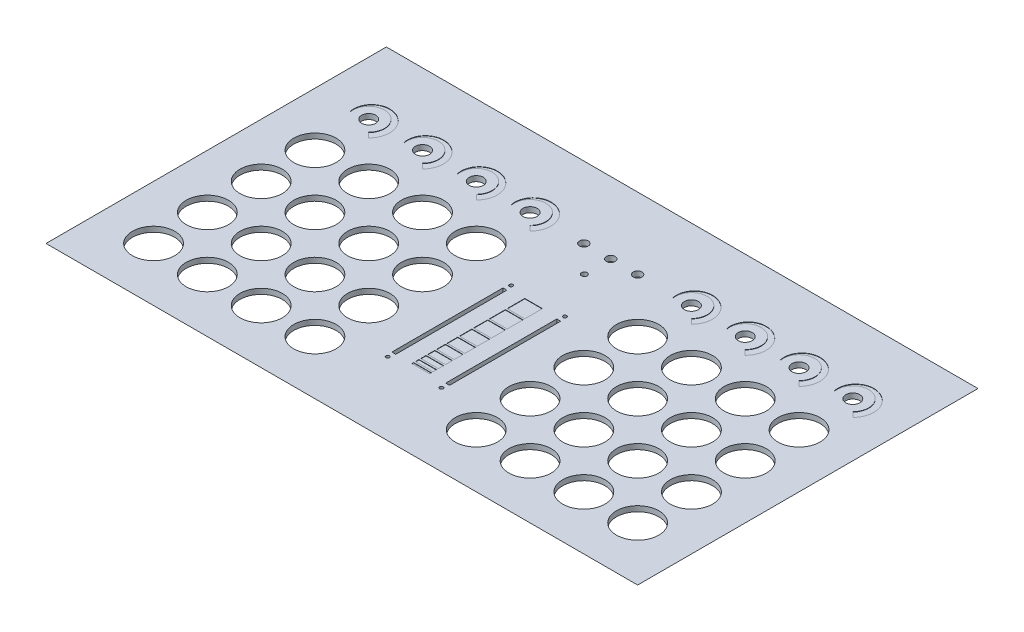
SolidWorks part; units mm, degrees
material "ABS"
ref_plane "Front Plane" through (0, 0, 0) normal (0, 0, 1) x (1, 0, 0)
ref_plane "Top Plane" through (0, 0, 0) normal (0, 1, 0) x (1, 0, 0)
ref_plane "Right Plane" through (0, 0, 0) normal (1, 0, 0) x (0, 0, -1)
sketch "Sketch2" plane through (0, 0, 0) normal (0, 1, 0) x (1, 0, 0)
  line L0 (0, 0) -> (91.5, 0) construction
  line L1 (0, 0) -> (0, 91.5) construction
  line L2 (122, 80.75) -> (122, 10.75) construction
  line L3 (120.9, 77.25) -> (123.1, 77.25)
  line L4 (120.9, 77.25) -> (120.9, 14.25)
  line L5 (120.9, 14.25) -> (123.1, 14.25)
  line L6 (123.1, 77.25) -> (123.1, 14.25)
  line L7 (91.5, 45.75) -> (137.25, 45.75) construction
  line L8 (91.5, 30.5) -> (91.5, 61) construction
  line L9 (0, 91.5) -> (0, 122) construction
  line L10 (0, 122) -> (91.5, 122) construction
  line L11 (0, 122) -> (30.5, 122) construction
  line L12 (137.25, -28.4189) -> (137.25, 162.5507) construction
  line L13 (274.5, 122) -> (244, 122) construction
  line L14 (274.5, 122) -> (183, 122) construction
  line L15 (274.5, 91.5) -> (274.5, 122) construction
  line L16 (183, 30.5) -> (183, 61) construction
  line L17 (152.5, 80.75) -> (152.5, 10.75) construction
  line L18 (274.5, 0) -> (274.5, 91.5) construction
  line L19 (274.5, 0) -> (183, 0) construction
  line L20 (151.4, 77.25) -> (151.4, 14.25)
  line L21 (153.6, 14.25) -> (151.4, 14.25)
  line L22 (153.6, 77.25) -> (153.6, 14.25)
  line L23 (153.6, 77.25) -> (151.4, 77.25)
  line L25 (-30.5, -30.5) -> (305, -30.5)
  line L26 (-30.5, -30.5) -> (-30.5, 162.5)
  line L27 (-30.5, 162.5) -> (305, 162.5)
  line L28 (305, -30.5) -> (305, 162.5)
  circle A0 centre (0, 0) radius 12
  circle A1 centre (30.5, 0) radius 12
  circle A2 centre (61, 0) radius 12
  circle A3 centre (91.5, 0) radius 12
  circle A4 centre (30.5, 30.5) radius 12
  circle A5 centre (61, 30.5) radius 12
  circle A6 centre (91.5, 30.5) radius 12
  circle A7 centre (30.5, 61) radius 12
  circle A8 centre (61, 61) radius 12
  circle A9 centre (91.5, 61) radius 12
  circle A10 centre (30.5, 91.5) radius 12
  circle A11 centre (61, 91.5) radius 12
  circle A12 centre (91.5, 91.5) radius 12
  circle A13 centre (0, 30.5) radius 12
  circle A14 centre (0, 61) radius 12
  circle A15 centre (0, 91.5) radius 12
  circle A16 centre (122, 80.75) radius 1
  circle A17 centre (122, 10.75) radius 1
  circle A18 centre (0, 122) radius 4
  circle A19 centre (30.5, 122) radius 4
  circle A20 centre (61, 122) radius 4
  circle A21 centre (91.5, 122) radius 4
  circle A22 centre (183, 122) radius 4
  circle A23 centre (213.5, 122) radius 4
  circle A24 centre (244, 122) radius 4
  circle A25 centre (274.5, 122) radius 4
  circle A26 centre (152.5, 10.75) radius 1
  circle A27 centre (152.5, 80.75) radius 1
  circle A28 centre (274.5, 91.5) radius 12
  circle A29 centre (274.5, 61) radius 12
  circle A30 centre (274.5, 30.5) radius 12
  circle A31 centre (183, 91.5) radius 12
  circle A32 centre (213.5, 91.5) radius 12
  circle A33 centre (244, 91.5) radius 12
  circle A34 centre (183, 61) radius 12
  circle A35 centre (213.5, 61) radius 12
  circle A36 centre (244, 61) radius 12
  circle A37 centre (183, 30.5) radius 12
  circle A38 centre (213.5, 30.5) radius 12
  circle A39 centre (244, 30.5) radius 12
  circle A40 centre (183, 0) radius 12
  circle A41 centre (213.5, 0) radius 12
  circle A42 centre (244, 0) radius 12
  circle A43 centre (274.5, 0) radius 12
  point P41 (122, 77.25)
  point P42 (120.9, 45.75)
  point P105 (153.6, 45.75)
  point P106 (152.5, 77.25)
  dimension "D1" = 24
  dimension "D8" = 2
  dimension "D12" = 8
  dimension "D4" = 30.5
  dimension "D5" = 30.5
  dimension "D6" = 63
  dimension "D7" = 2.2
  dimension "D9" = 3.5
  dimension "D10" = 3.5
  dimension "D11" = 30.5
  dimension "D14" = 30.5
  dimension "D15" = 30.5
  dimension "D16" = 15.25
  dimension "D17" = 30.5
  dimension "D18" = 30.5
  dimension "D19" = 30.5
  dimension "D20" = 40.5
  dimension "D2" = 4
  dimension "D3" = 4
  dimension "D13" = 4
extrude "Boss-Extrude1" add sketch "Sketch2" along normal blind 3
sketch "Sketch27" plane through (0, 3, 0) normal (0, 1, 0) x (1, 0, 0)
  line L0 (0, 122) -> (-6.364, 115.636) construction
  line L1 (-6.364, 115.636) -> (6.364, 115.636) construction
  line L2 (6.364, 115.636) -> (0, 122) construction
  line L3 (0, 131) -> (0, 135) construction
  line L4 (6.364, 115.636) -> (9.1924, 112.8076)
  line L5 (0, 122) -> (0.8429, 122.8429) construction
  line L6 (36.864, 115.636) -> (39.6924, 112.8076)
  line L7 (30.5, 122) -> (24.136, 115.636) construction
  line L8 (24.136, 115.636) -> (36.864, 115.636) construction
  line L9 (36.864, 115.636) -> (30.5, 122) construction
  line L10 (30.5, 131) -> (30.5, 135) construction
  line L11 (30.5, 122) -> (31.3429, 122.8429) construction
  line L12 (67.364, 115.636) -> (70.1924, 112.8076)
  line L13 (61, 122) -> (54.636, 115.636) construction
  line L14 (54.636, 115.636) -> (67.364, 115.636) construction
  line L15 (67.364, 115.636) -> (61, 122) construction
  line L16 (61, 131) -> (61, 135) construction
  line L17 (61, 122) -> (61.8429, 122.8429) construction
  line L18 (97.864, 115.636) -> (100.6924, 112.8076)
  line L19 (91.5, 122) -> (85.136, 115.636) construction
  line L20 (85.136, 115.636) -> (97.864, 115.636) construction
  line L21 (97.864, 115.636) -> (91.5, 122) construction
  line L22 (91.5, 131) -> (91.5, 135) construction
  line L23 (91.5, 122) -> (92.3429, 122.8429) construction
  line L24 (189.364, 115.636) -> (192.1924, 112.8076)
  line L25 (219.864, 115.636) -> (222.6924, 112.8076)
  line L26 (250.364, 115.636) -> (253.1924, 112.8076)
  line L27 (280.864, 115.636) -> (283.6924, 112.8076)
  line L28 (183, 122) -> (176.636, 115.636) construction
  line L29 (176.636, 115.636) -> (189.364, 115.636) construction
  line L30 (189.364, 115.636) -> (183, 122) construction
  line L31 (183, 131) -> (183, 135) construction
  line L32 (183, 122) -> (183.8429, 122.8429) construction
  line L33 (213.5, 122) -> (207.136, 115.636) construction
  line L34 (207.136, 115.636) -> (219.864, 115.636) construction
  line L35 (219.864, 115.636) -> (213.5, 122) construction
  line L36 (213.5, 131) -> (213.5, 135) construction
  line L37 (213.5, 122) -> (214.3429, 122.8429) construction
  line L38 (244, 122) -> (237.636, 115.636) construction
  line L39 (237.636, 115.636) -> (250.364, 115.636) construction
  line L40 (250.364, 115.636) -> (244, 122) construction
  line L41 (244, 131) -> (244, 135) construction
  line L42 (244, 122) -> (244.8429, 122.8429) construction
  line L43 (274.5, 122) -> (268.136, 115.636) construction
  line L44 (268.136, 115.636) -> (280.864, 115.636) construction
  line L45 (280.864, 115.636) -> (274.5, 122) construction
  line L46 (274.5, 131) -> (274.5, 135) construction
  line L47 (274.5, 122) -> (275.3429, 122.8429) construction
  line L48 (123.1, 14.25) -> (151.4, 14.25) construction
  line L49 (123.1, 77.25) -> (151.4, 77.25) construction
  line L50 (137.25, 14.25) -> (137.25, 77.25) construction
  line L51 (132.25, 15.25) -> (142.25, 15.25)
  line L52 (132.25, 14.25) -> (142.25, 14.25)
  line L53 (132.25, 47.25) -> (132.25, 48.25)
  line L54 (132.25, 14.25) -> (132.25, 15.25)
  line L55 (132.25, 15.25) -> (142.25, 15.25)
  line L56 (142.25, 14.25) -> (142.25, 15.25)
  line L57 (132.25, 16.25) -> (142.25, 16.25)
  line L58 (142.25, 47.25) -> (142.25, 48.25)
  line L59 (132.25, 16.25) -> (142.25, 16.25)
  line L60 (132.25, 16.25) -> (132.25, 17.25)
  line L61 (132.25, 77.25) -> (132.25, 78.25)
  line L62 (142.25, 16.25) -> (142.25, 17.25)
  line L63 (132.25, 78.25) -> (142.25, 78.25)
  line L64 (132.25, 17.25) -> (132.25, 18.25)
  line L65 (132.25, 18.25) -> (142.25, 18.25)
  line L66 (142.25, 17.25) -> (142.25, 18.25)
  line L67 (132.25, 18.25) -> (142.25, 18.25)
  line L68 (142.25, 78.25) -> (142.25, 77.25)
  line L69 (132.25, 19.25) -> (142.25, 19.25)
  line L71 (132.25, 19.25) -> (142.25, 19.25)
  line L72 (132.25, 19.25) -> (132.25, 20.25)
  line L74 (142.25, 19.25) -> (142.25, 20.25)
  line L76 (132.25, 20.25) -> (132.25, 21.25)
  line L78 (142.25, 20.25) -> (142.25, 21.25)
  line L80 (132.25, 21.25) -> (132.25, 22.25)
  line L81 (132.25, 22.25) -> (142.25, 22.25)
  line L82 (142.25, 21.25) -> (142.25, 22.25)
  line L83 (132.25, 22.25) -> (142.25, 22.25)
  line L85 (132.25, 23.25) -> (142.25, 23.25)
  line L87 (132.25, 23.25) -> (142.25, 23.25)
  line L88 (132.25, 23.25) -> (132.25, 24.25)
  line L90 (142.25, 23.25) -> (142.25, 24.25)
  line L92 (132.25, 24.25) -> (132.25, 25.25)
  line L94 (142.25, 24.25) -> (142.25, 25.25)
  line L96 (132.25, 25.25) -> (132.25, 26.25)
  line L98 (142.25, 25.25) -> (142.25, 26.25)
  line L100 (132.25, 26.25) -> (132.25, 27.25)
  line L101 (132.25, 27.25) -> (142.25, 27.25)
  line L102 (142.25, 26.25) -> (142.25, 27.25)
  line L103 (132.25, 27.25) -> (142.25, 27.25)
  line L105 (132.25, 28.25) -> (142.25, 28.25)
  line L107 (132.25, 28.25) -> (142.25, 28.25)
  line L108 (132.25, 28.25) -> (132.25, 29.25)
  line L110 (142.25, 28.25) -> (142.25, 29.25)
  line L112 (132.25, 29.25) -> (132.25, 30.25)
  line L114 (142.25, 29.25) -> (142.25, 30.25)
  line L116 (132.25, 30.25) -> (132.25, 31.25)
  line L118 (142.25, 30.25) -> (142.25, 31.25)
  line L120 (132.25, 31.25) -> (132.25, 32.25)
  line L122 (142.25, 31.25) -> (142.25, 32.25)
  line L124 (132.25, 32.25) -> (132.25, 33.25)
  line L125 (132.25, 33.25) -> (142.25, 33.25)
  line L126 (142.25, 32.25) -> (142.25, 33.25)
  line L127 (132.25, 33.25) -> (142.25, 33.25)
  line L129 (132.25, 34.25) -> (142.25, 34.25)
  line L131 (132.25, 34.25) -> (142.25, 34.25)
  line L132 (132.25, 34.25) -> (132.25, 35.25)
  line L134 (142.25, 34.25) -> (142.25, 35.25)
  line L136 (132.25, 35.25) -> (132.25, 36.25)
  line L138 (142.25, 35.25) -> (142.25, 36.25)
  line L140 (132.25, 36.25) -> (132.25, 37.25)
  line L142 (142.25, 36.25) -> (142.25, 37.25)
  line L144 (132.25, 37.25) -> (132.25, 38.25)
  line L146 (142.25, 37.25) -> (142.25, 38.25)
  line L148 (132.25, 38.25) -> (132.25, 39.25)
  line L150 (142.25, 38.25) -> (142.25, 39.25)
  line L152 (132.25, 39.25) -> (132.25, 40.25)
  line L153 (132.25, 40.25) -> (142.25, 40.25)
  line L154 (142.25, 39.25) -> (142.25, 40.25)
  line L155 (132.25, 40.25) -> (142.25, 40.25)
  line L157 (132.25, 41.25) -> (142.25, 41.25)
  line L159 (132.25, 41.25) -> (142.25, 41.25)
  line L160 (132.25, 41.25) -> (132.25, 42.25)
  line L162 (142.25, 41.25) -> (142.25, 42.25)
  line L164 (132.25, 42.25) -> (132.25, 43.25)
  line L166 (142.25, 42.25) -> (142.25, 43.25)
  line L168 (132.25, 43.25) -> (132.25, 44.25)
  line L170 (142.25, 43.25) -> (142.25, 44.25)
  line L172 (132.25, 44.25) -> (132.25, 45.25)
  line L174 (142.25, 44.25) -> (142.25, 45.25)
  line L176 (132.25, 45.25) -> (132.25, 46.25)
  line L178 (142.25, 45.25) -> (142.25, 46.25)
  line L180 (132.25, 46.25) -> (132.25, 47.25)
  line L182 (142.25, 46.25) -> (142.25, 47.25)
  line L185 (132.25, 48.25) -> (142.25, 48.25)
  line L187 (132.25, 48.25) -> (142.25, 48.25)
  line L189 (132.25, 49.25) -> (142.25, 49.25)
  line L191 (132.25, 49.25) -> (142.25, 49.25)
  line L192 (132.25, 49.25) -> (132.25, 50.25)
  line L194 (142.25, 49.25) -> (142.25, 50.25)
  line L196 (132.25, 50.25) -> (132.25, 51.25)
  line L198 (142.25, 50.25) -> (142.25, 51.25)
  line L200 (132.25, 51.25) -> (132.25, 52.25)
  line L202 (142.25, 51.25) -> (142.25, 52.25)
  line L204 (132.25, 52.25) -> (132.25, 53.25)
  line L206 (142.25, 52.25) -> (142.25, 53.25)
  line L208 (132.25, 53.25) -> (132.25, 54.25)
  line L210 (142.25, 53.25) -> (142.25, 54.25)
  line L212 (132.25, 54.25) -> (132.25, 55.25)
  line L214 (142.25, 54.25) -> (142.25, 55.25)
  line L216 (132.25, 55.25) -> (132.25, 56.25)
  line L218 (142.25, 55.25) -> (142.25, 56.25)
  line L220 (132.25, 56.25) -> (132.25, 57.25)
  line L221 (132.25, 57.25) -> (142.25, 57.25)
  line L222 (142.25, 56.25) -> (142.25, 57.25)
  line L223 (132.25, 57.25) -> (142.25, 57.25)
  line L225 (132.25, 58.25) -> (142.25, 58.25)
  line L227 (132.25, 58.25) -> (142.25, 58.25)
  line L228 (132.25, 58.25) -> (132.25, 59.25)
  line L230 (142.25, 58.25) -> (142.25, 59.25)
  line L232 (132.25, 59.25) -> (132.25, 60.25)
  line L234 (142.25, 59.25) -> (142.25, 60.25)
  line L236 (132.25, 60.25) -> (132.25, 61.25)
  line L238 (142.25, 60.25) -> (142.25, 61.25)
  line L240 (132.25, 61.25) -> (132.25, 62.25)
  line L242 (142.25, 61.25) -> (142.25, 62.25)
  line L244 (132.25, 62.25) -> (132.25, 63.25)
  line L246 (142.25, 62.25) -> (142.25, 63.25)
  line L248 (132.25, 63.25) -> (132.25, 64.25)
  line L250 (142.25, 63.25) -> (142.25, 64.25)
  line L252 (132.25, 64.25) -> (132.25, 65.25)
  line L254 (142.25, 64.25) -> (142.25, 65.25)
  line L256 (132.25, 65.25) -> (132.25, 66.25)
  line L258 (142.25, 65.25) -> (142.25, 66.25)
  line L260 (132.25, 66.25) -> (132.25, 67.25)
  line L261 (132.25, 67.25) -> (142.25, 67.25)
  line L262 (142.25, 66.25) -> (142.25, 67.25)
  line L263 (132.25, 67.25) -> (142.25, 67.25)
  line L265 (132.25, 68.25) -> (142.25, 68.25)
  line L267 (132.25, 68.25) -> (142.25, 68.25)
  line L268 (132.25, 68.25) -> (132.25, 69.25)
  line L270 (142.25, 68.25) -> (142.25, 69.25)
  line L272 (132.25, 69.25) -> (132.25, 70.25)
  line L274 (142.25, 69.25) -> (142.25, 70.25)
  line L276 (132.25, 70.25) -> (132.25, 71.25)
  line L278 (142.25, 70.25) -> (142.25, 71.25)
  line L280 (132.25, 71.25) -> (132.25, 72.25)
  line L282 (142.25, 71.25) -> (142.25, 72.25)
  line L284 (132.25, 72.25) -> (132.25, 73.25)
  line L286 (142.25, 72.25) -> (142.25, 73.25)
  line L288 (132.25, 73.25) -> (132.25, 74.25)
  line L290 (142.25, 73.25) -> (142.25, 74.25)
  line L292 (132.25, 74.25) -> (132.25, 75.25)
  line L294 (142.25, 74.25) -> (142.25, 75.25)
  line L296 (132.25, 75.25) -> (132.25, 76.25)
  line L298 (142.25, 75.25) -> (142.25, 76.25)
  line L300 (132.25, 76.25) -> (132.25, 77.25)
  line L302 (142.25, 76.25) -> (142.25, 77.25)
  line L303 (142.25, 15.25) -> (142.25, 16.25) [skipped]
  line L304 (132.25, 15.25) -> (132.25, 16.25) [skipped]
  line L305 (137.25, 17.25) -> (142.25, 17.25) [skipped]
  line L306 (137.25, 17.25) -> (142.25, 17.25) [skipped]
  line L307 (132.25, 18.25) -> (132.25, 19.25) [skipped]
  line L308 (142.25, 18.25) -> (142.25, 19.25) [skipped]
  line L309 (132.25, 20.25) -> (137.25, 20.25) [skipped]
  line L310 (132.25, 20.25) -> (137.25, 20.25) [skipped]
  line L311 (132.25, 21.25) -> (137.25, 21.25) [skipped]
  line L312 (132.25, 21.25) -> (137.25, 21.25) [skipped]
  line L313 (132.25, 22.25) -> (132.25, 23.25) [skipped]
  line L314 (142.25, 22.25) -> (142.25, 23.25) [skipped]
  line L315 (132.25, 24.25) -> (137.25, 24.25) [skipped]
  line L316 (132.25, 24.25) -> (137.25, 24.25) [skipped]
  line L317 (132.25, 25.25) -> (137.25, 25.25) [skipped]
  line L318 (132.25, 25.25) -> (137.25, 25.25) [skipped]
  line L319 (132.25, 26.25) -> (137.25, 26.25) [skipped]
  line L320 (132.25, 26.25) -> (137.25, 26.25) [skipped]
  line L321 (132.25, 27.25) -> (132.25, 28.25) [skipped]
  line L322 (142.25, 27.25) -> (142.25, 28.25) [skipped]
  line L323 (132.25, 32.25) -> (137.25, 32.25) [skipped]
  line L324 (132.25, 32.25) -> (137.25, 32.25) [skipped]
  line L325 (132.25, 31.25) -> (137.25, 31.25) [skipped]
  line L326 (132.25, 31.25) -> (137.25, 31.25) [skipped]
  line L327 (132.25, 30.25) -> (137.25, 30.25) [skipped]
  line L328 (132.25, 30.25) -> (137.25, 30.25) [skipped]
  line L329 (132.25, 29.25) -> (137.25, 29.25) [skipped]
  line L330 (132.25, 29.25) -> (137.25, 29.25) [skipped]
  line L331 (132.25, 33.25) -> (132.25, 34.25) [skipped]
  line L332 (142.25, 33.25) -> (142.25, 34.25) [skipped]
  line L333 (132.25, 35.25) -> (137.25, 35.25) [skipped]
  line L334 (132.25, 35.25) -> (137.25, 35.25) [skipped]
  line L335 (132.25, 36.25) -> (137.25, 36.25) [skipped]
  line L336 (132.25, 36.25) -> (137.25, 36.25) [skipped]
  line L337 (132.25, 37.25) -> (137.25, 37.25) [skipped]
  line L338 (132.25, 37.25) -> (137.25, 37.25) [skipped]
  line L339 (132.25, 38.25) -> (137.25, 38.25) [skipped]
  line L340 (132.25, 38.25) -> (137.25, 38.25) [skipped]
  line L341 (132.25, 39.25) -> (137.25, 39.25) [skipped]
  line L342 (132.25, 39.25) -> (137.25, 39.25) [skipped]
  line L343 (132.25, 40.25) -> (132.25, 41.25) [skipped]
  line L344 (142.25, 40.25) -> (142.25, 41.25) [skipped]
  line L345 (132.25, 43.25) -> (137.25, 43.25) [skipped]
  line L346 (132.25, 43.25) -> (137.25, 43.25) [skipped]
  line L347 (132.25, 42.25) -> (137.25, 42.25) [skipped]
  line L348 (132.25, 42.25) -> (137.25, 42.25) [skipped]
  line L349 (132.25, 44.25) -> (137.25, 44.25) [skipped]
  line L350 (132.25, 44.25) -> (137.25, 44.25) [skipped]
  line L351 (132.25, 45.25) -> (137.25, 45.25) [skipped]
  line L352 (132.25, 45.25) -> (137.25, 45.25) [skipped]
  line L353 (132.25, 46.25) -> (137.25, 46.25) [skipped]
  line L354 (132.25, 46.25) -> (137.25, 46.25) [skipped]
  line L355 (132.25, 47.25) -> (132.25, 48.25) [skipped]
  line L356 (142.25, 47.25) -> (142.25, 48.25) [skipped]
  line L357 (142.25, 48.25) -> (142.25, 49.25) [skipped]
  line L358 (132.25, 48.25) -> (132.25, 49.25) [skipped]
  line L359 (137.25, 47.25) -> (142.25, 47.25) [skipped]
  line L360 (137.25, 47.25) -> (142.25, 47.25) [skipped]
  line L361 (132.25, 51.25) -> (137.25, 51.25) [skipped]
  line L362 (132.25, 51.25) -> (137.25, 51.25) [skipped]
  line L363 (132.25, 50.25) -> (137.25, 50.25) [skipped]
  line L364 (132.25, 50.25) -> (137.25, 50.25) [skipped]
  line L365 (132.25, 52.25) -> (137.25, 52.25) [skipped]
  line L366 (132.25, 52.25) -> (137.25, 52.25) [skipped]
  line L367 (132.25, 53.25) -> (137.25, 53.25) [skipped]
  line L368 (132.25, 53.25) -> (137.25, 53.25) [skipped]
  line L369 (132.25, 54.25) -> (137.25, 54.25) [skipped]
  line L370 (132.25, 54.25) -> (137.25, 54.25) [skipped]
  line L371 (132.25, 55.25) -> (137.25, 55.25) [skipped]
  line L372 (132.25, 55.25) -> (137.25, 55.25) [skipped]
  line L373 (132.25, 56.25) -> (137.25, 56.25) [skipped]
  line L374 (132.25, 56.25) -> (137.25, 56.25) [skipped]
  line L375 (142.25, 57.25) -> (142.25, 58.25) [skipped]
  line L376 (132.25, 57.25) -> (132.25, 58.25) [skipped]
  line L377 (137.25, 60.25) -> (142.25, 60.25) [skipped]
  line L378 (137.25, 60.25) -> (142.25, 60.25) [skipped]
  line L379 (137.25, 61.25) -> (142.25, 61.25) [skipped]
  line L380 (137.25, 61.25) -> (142.25, 61.25) [skipped]
  line L381 (137.25, 62.25) -> (142.25, 62.25) [skipped]
  line L382 (137.25, 62.25) -> (142.25, 62.25) [skipped]
  line L383 (137.25, 63.25) -> (142.25, 63.25) [skipped]
  line L384 (137.25, 63.25) -> (142.25, 63.25) [skipped]
  line L385 (137.25, 64.25) -> (142.25, 64.25) [skipped]
  line L386 (137.25, 64.25) -> (142.25, 64.25) [skipped]
  line L387 (137.25, 65.25) -> (142.25, 65.25) [skipped]
  line L388 (137.25, 65.25) -> (142.25, 65.25) [skipped]
  line L389 (137.25, 66.25) -> (142.25, 66.25) [skipped]
  line L390 (137.25, 66.25) -> (142.25, 66.25) [skipped]
  line L391 (140.5009, 59.25) -> (142.25, 59.25) [skipped]
  line L392 (140.5009, 59.25) -> (142.25, 59.25) [skipped]
  line L393 (142.25, 67.25) -> (142.25, 68.25) [skipped]
  line L394 (132.25, 67.25) -> (132.25, 68.25) [skipped]
  line L395 (137.25, 69.25) -> (142.25, 69.25) [skipped]
  line L396 (137.25, 69.25) -> (142.25, 69.25) [skipped]
  line L397 (137.25, 70.25) -> (142.25, 70.25) [skipped]
  line L398 (137.25, 70.25) -> (142.25, 70.25) [skipped]
  line L399 (137.25, 71.25) -> (142.25, 71.25) [skipped]
  line L400 (137.25, 71.25) -> (142.25, 71.25) [skipped]
  line L401 (137.25, 72.25) -> (142.25, 72.25) [skipped]
  line L402 (137.25, 72.25) -> (142.25, 72.25) [skipped]
  line L403 (137.25, 73.25) -> (142.25, 73.25) [skipped]
  line L404 (137.25, 73.25) -> (142.25, 73.25) [skipped]
  line L405 (137.25, 74.25) -> (142.25, 74.25) [skipped]
  line L406 (137.25, 74.25) -> (142.25, 74.25) [skipped]
  line L407 (137.25, 75.25) -> (142.25, 75.25) [skipped]
  line L408 (137.25, 75.25) -> (142.25, 75.25) [skipped]
  line L409 (137.25, 76.25) -> (142.25, 76.25) [skipped]
  line L410 (137.25, 76.25) -> (142.25, 76.25) [skipped]
  line L411 (132.25, 77.25) -> (142.25, 77.25) [skipped]
  arc A0 (6.364, 115.636) -> (-8.8817, 120.5456) centre (0, 122) ccw
  arc A1 (9.1924, 112.8076) -> (0, 135) centre (0, 122) ccw construction
  arc A2 (0, 133) -> (-9.0777, 120.5065) centre (0.8429, 122.8429) ccw
  arc A3 (9.1924, 112.8076) -> (0, 133) centre (0.8167, 121.1833) ccw
  arc A4 (36.864, 115.636) -> (21.6183, 120.5456) centre (30.5, 122) ccw
  arc A5 (39.6924, 112.8076) -> (30.5, 135) centre (30.5, 122) ccw construction
  arc A6 (30.5, 133) -> (21.4223, 120.5065) centre (31.3429, 122.8429) ccw
  arc A7 (39.6924, 112.8076) -> (30.5, 133) centre (31.3167, 121.1833) ccw
  arc A8 (67.364, 115.636) -> (52.1183, 120.5456) centre (61, 122) ccw
  arc A9 (70.1924, 112.8076) -> (61, 135) centre (61, 122) ccw construction
  arc A10 (61, 133) -> (51.9223, 120.5065) centre (61.8429, 122.8429) ccw
  arc A11 (70.1924, 112.8076) -> (61, 133) centre (61.8167, 121.1833) ccw
  arc A12 (97.864, 115.636) -> (82.6183, 120.5456) centre (91.5, 122) ccw
  arc A13 (100.6924, 112.8076) -> (91.5, 135) centre (91.5, 122) ccw construction
  arc A14 (91.5, 133) -> (82.4223, 120.5065) centre (92.3429, 122.8429) ccw
  arc A15 (100.6924, 112.8076) -> (91.5, 133) centre (92.3167, 121.1833) ccw
  arc A16 (189.364, 115.636) -> (174.1183, 120.5456) centre (183, 122) ccw
  arc A17 (183, 133) -> (173.9223, 120.5065) centre (183.8429, 122.8429) ccw
  arc A18 (192.1924, 112.8076) -> (183, 133) centre (183.8167, 121.1833) ccw
  arc A19 (219.864, 115.636) -> (204.6183, 120.5456) centre (213.5, 122) ccw
  arc A20 (213.5, 133) -> (204.4223, 120.5065) centre (214.3429, 122.8429) ccw
  arc A21 (222.6924, 112.8076) -> (213.5, 133) centre (214.3167, 121.1833) ccw
  arc A22 (250.364, 115.636) -> (235.1183, 120.5456) centre (244, 122) ccw
  arc A23 (244, 133) -> (234.9223, 120.5065) centre (244.8429, 122.8429) ccw
  arc A24 (253.1924, 112.8076) -> (244, 133) centre (244.8167, 121.1833) ccw
  arc A25 (280.864, 115.636) -> (265.6183, 120.5456) centre (274.5, 122) ccw
  arc A26 (274.5, 133) -> (265.4223, 120.5065) centre (275.3429, 122.8429) ccw
  arc A27 (283.6924, 112.8076) -> (274.5, 133) centre (275.3167, 121.1833) ccw
  arc A28 (192.1924, 112.8076) -> (183, 135) centre (183, 122) ccw construction
  arc A29 (222.6924, 112.8076) -> (213.5, 135) centre (213.5, 122) ccw construction
  arc A30 (253.1924, 112.8076) -> (244, 135) centre (244, 122) ccw construction
  arc A31 (283.6924, 112.8076) -> (274.5, 135) centre (274.5, 122) ccw construction
  arc A32 (265.6183, 120.5456) -> (265.4223, 120.5065) centre (265.5196, 120.5294) cw
  arc A33 (235.1183, 120.5456) -> (234.9223, 120.5065) centre (235.0196, 120.5294) cw
  arc A34 (204.6183, 120.5456) -> (204.4223, 120.5065) centre (204.5196, 120.5294) cw
  arc A35 (174.1183, 120.5456) -> (173.9223, 120.5065) centre (174.0196, 120.5294) cw
  arc A36 (82.6183, 120.5456) -> (82.4223, 120.5065) centre (82.5196, 120.5294) cw
  arc A37 (52.1183, 120.5456) -> (51.9223, 120.5065) centre (52.0196, 120.5294) cw
  arc A38 (21.6183, 120.5456) -> (21.4223, 120.5065) centre (21.5196, 120.5294) cw
  arc A39 (-9.0777, 120.5065) -> (-8.8817, 120.5456) centre (-8.9804, 120.5294) ccw
  point P11 (0, 133)
  point P20 (30.5, 133)
  point P30 (61, 133)
  point P40 (91.5, 133)
  point P50 (183, 133)
  point P59 (213.5, 133)
  point P69 (244, 133)
  point P79 (274.5, 133)
  point P95 (137.25, 14.25)
  point P102 (137.25, 15.25)
  point P107 (137.25, 16.25)
  point P112 (137.25, 17.25)
  point P117 (137.25, 18.25)
  point P122 (137.25, 19.25)
  point P127 (137.25, 20.25)
  point P132 (137.25, 21.25)
  point P137 (137.25, 22.25)
  point P142 (137.25, 23.25)
  point P147 (137.25, 24.25)
  point P152 (137.25, 25.25)
  point P157 (137.25, 26.25)
  point P162 (137.25, 27.25)
  point P167 (137.25, 28.25)
  point P172 (137.25, 29.25)
  point P177 (137.25, 30.25)
  point P182 (137.25, 31.25)
  point P187 (137.25, 32.25)
  point P192 (137.25, 33.25)
  point P197 (137.25, 34.25)
  point P202 (137.25, 35.25)
  point P207 (137.25, 36.25)
  point P212 (137.25, 37.25)
  point P217 (137.25, 38.25)
  point P222 (137.25, 39.25)
  point P227 (137.25, 40.25)
  point P232 (137.25, 41.25)
  point P237 (137.25, 42.25)
  point P242 (137.25, 43.25)
  point P247 (137.25, 44.25)
  point P252 (137.25, 45.25)
  point P257 (137.25, 46.25)
  point P262 (137.25, 47.25)
  point P267 (137.25, 48.25)
  point P272 (137.25, 49.25)
  point P277 (137.25, 50.25)
  point P282 (137.25, 51.25)
  point P287 (137.25, 52.25)
  point P292 (137.25, 53.25)
  point P297 (137.25, 54.25)
  point P302 (137.25, 55.25)
  point P307 (137.25, 56.25)
  point P312 (137.25, 57.25)
  point P317 (137.25, 58.25)
  point P322 (137.25, 59.25)
  point P327 (137.25, 60.25)
  point P332 (137.25, 61.25)
  point P337 (137.25, 62.25)
  point P342 (137.25, 63.25)
  point P347 (137.25, 64.25)
  point P352 (137.25, 65.25)
  point P357 (137.25, 66.25)
  point P362 (137.25, 67.25)
  point P367 (137.25, 68.25)
  point P372 (137.25, 69.25)
  point P377 (137.25, 70.25)
  point P382 (137.25, 71.25)
  point P387 (137.25, 72.25)
  point P392 (137.25, 73.25)
  point P397 (137.25, 74.25)
  point P402 (137.25, 75.25)
  point P407 (137.25, 76.25)
  dimension "D1" = 18
  dimension "D3" = 26
  dimension "D10" = 0.1
  dimension "D2" = 270
  dimension "D6" = 10
  dimension "D7" = 1
  dimension "D8" = 63
  dimension "D9" = 1
  dimension "D4" = 4
  dimension "D5" = 2
extrude "Cut-Extrude14" cut sketch "Sketch27" against normal blind 0.2 contours L6 A7 A6 A4 | L24 A18 A17 A16 | L25 A21 A20 A19 | L26 A24 A23 A22 | L27 A27 A26 A25 | L52 L56 L51 L54 | L62 L66 L65 L64 L60 L57 | L78 L82 L81 L80 L76 L72 L69 L74 | L98 L102 L101 L100 L96 L92 L88 L85 L90 L94 | L122 L126 L125 L124 L120 L116 L112 L108 L105 L110 L114 L118 | L150 L154 L153 L152 L148 L144 L140 L136 L132 L129 L134 L138 L142 L146 | L298 L302 L68 L63 L61 L300 L296 L292 L288 L284 L280 L276 L272 L268 L265 L270 L274 L278 L282 L286 L290 L294 | L258 L262 L261 L260 L256 L252 L248 L244 L240 L236 L232 L228 L225 L230 L234 L238 L242 L246 L250 L254 | L218 L222 L221 L220 L216 L212 L208 L204 L200 L196 L192 L189 L194 L198 L202 L206 L210 L214 | L185 L53 L180 L176 L172 L168 L164 L160 L157 L162 L166 L170 L174 L178 L182 L58 | A0 A39 A2 A3 L4 | A8 A37 A10 A11 L12 | A12 A36 A14 A15 L18 region at (33.3503, 3, -130.8513) region at (185.8503, 3, -130.8513) region at (216.3503, 3, -130.8513) region at (246.8503, 3, -130.8513) region at (277.3503, 3, -130.8513) region at (137.25, 3, -14.75) region at (132.352, 3, -16.75) region at (137.25, 3, -20.75) region at (132.3577, 3, -23.75) region at (137.25, 3, -30.75) region at (132.3666, 3, -34.75) region at (137.25, 3, -44.75) region at (132.3781, 3, -49.75) region at (137.25, 3, -62.75) region at (137.25, 3, -72.75) region at (137.25, 3, -77.75)
sketch "Sketch3" plane through (0, 3, 0) normal (0, 1, 0) x (1, 0, 0)
  line L0 (91.5, 122) -> (183, 122) construction
  line L1 (137.25, 160.5) -> (137.25, 122) construction
  line L3 (122, 80.75) -> (122, 122) construction
  line L4 (152.5, 122) -> (152.5, 80.75) construction
  line L5 (137.25, 122) -> (137.25, 107) construction
  circle A0 centre (122, 122) radius 2.5
  circle A1 centre (137.25, 122) radius 2.5
  circle A2 centre (152.5, 122) radius 2.5
  circle A3 centre (137.25, 107) radius 1.6
  dimension "D1" = 5
  dimension "D2" = 3.2
  dimension "D3" = 15
extrude "Cut-Extrude1" cut sketch "Sketch3" against normal blind 10
chamfer "Chamfer2" distance 3 angle 45 4 edges at (-30.5, 0, -66) (137.25, 0, 30.5) (305, 0, -66) (137.25, 0, -162.5)
